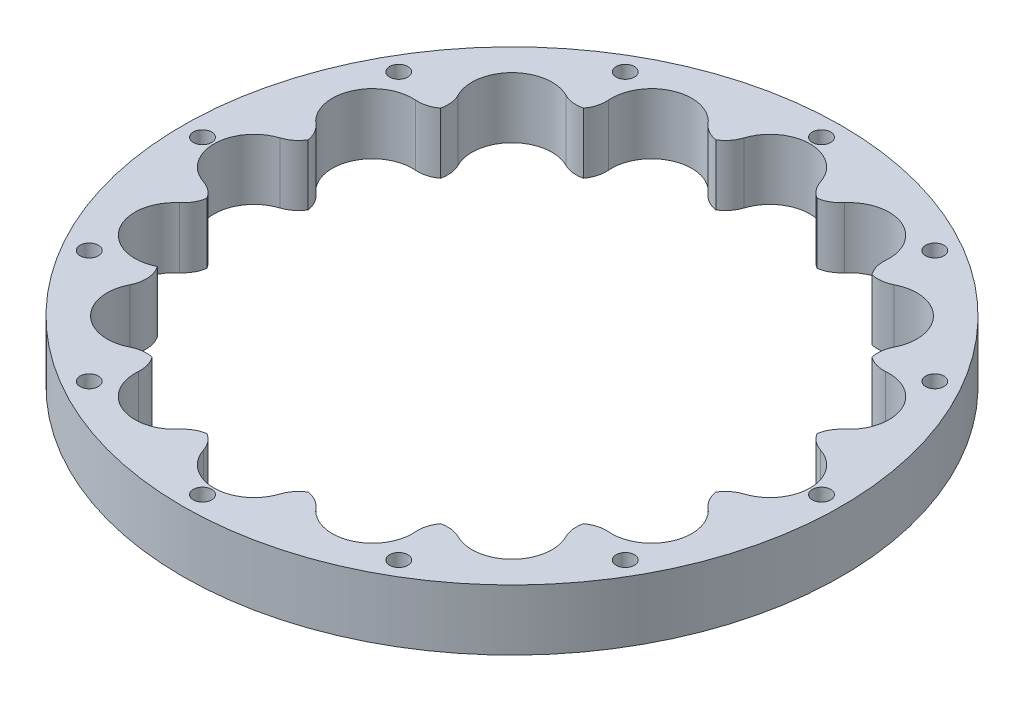
SolidWorks part; units mm, degrees
ref_plane "Front Plane" through (0, 0, 0) normal (0, 0, 1) x (1, 0, 0)
ref_plane "Top Plane" through (0, 0, 0) normal (0, 1, 0) x (1, 0, 0)
ref_plane "Right Plane" through (0, 0, 0) normal (1, 0, 0) x (0, 0, -1)
sketch "Sketch1" plane through (0, 0, 0) normal (0, 1, 0) x (1, 0, 0)
  circle A0 centre (0, 0) radius 45
  circle A1 centre (0, 45) radius 7
  circle A2 centre (17.2208, 41.5746) radius 7
  circle A3 centre (31.8198, 31.8198) radius 7
  circle A4 centre (41.5746, 17.2208) radius 7
  circle A5 centre (45, 0) radius 7
  circle A6 centre (41.5746, -17.2208) radius 7
  circle A7 centre (31.8198, -31.8198) radius 7
  circle A8 centre (17.2208, -41.5746) radius 7
  circle A9 centre (0, -45) radius 7
  circle A10 centre (-17.2208, -41.5746) radius 7
  circle A11 centre (-31.8198, -31.8198) radius 7
  circle A12 centre (0, 0) radius 57.5
  circle A13 centre (0, 0) radius 54 construction
  circle A14 centre (0, 54) radius 1.6
  circle A15 centre (27, 46.7654) radius 1.6
  circle A16 centre (46.7654, 27) radius 1.6
  circle A17 centre (54, 0) radius 1.6
  circle A18 centre (46.7654, -27) radius 1.6
  circle A19 centre (27, -46.7654) radius 1.6
  circle A20 centre (0, -54) radius 1.6
  circle A21 centre (-27, -46.7654) radius 1.6
  circle A22 centre (-46.7654, -27) radius 1.6
  circle A23 centre (-54, 0) radius 1.6
  circle A24 centre (-46.7654, 27) radius 1.6
  circle A25 centre (-27, 46.7654) radius 1.6
  circle A26 centre (-41.5746, -17.2208) radius 7
  circle A27 centre (-45, 0) radius 7
  circle A28 centre (-41.5746, 17.2208) radius 7
  circle A29 centre (-31.8198, 31.8198) radius 7
  circle A30 centre (-17.2208, 41.5746) radius 7
  point P27 (0, 0)
  point P54 (0, 0)
  dimension "D1" = 90
  dimension "D2" = 14
  dimension "D4" = 115
  dimension "D5" = 108
  dimension "D6" = 3.2
  dimension "D3" = 16
  dimension "D7" = 12
extrude "Boss-Extrude1" add sketch "Sketch1" along normal blind 10.6 contours A12 A25 A24 A23 A22 A21 A20 A19 A18 A17 A16 A15 A14 A11 A0 A1 A2 A3 A4 A5 A6 A7 A8 A9 A10 region at (-55.8737, 0, 0)
fillet "Fillet1" radius 5 31 edges at (38.4009, 5.3, -23.46) (36.3696, 5.3, -26.5001) (44.4556, 5.3, -6.9788) (43.7422, 5.3, -10.5648) (44.4556, 5.3, 6.9788) (43.7422, 5.3, 10.5648) (38.4009, 5.3, 23.46) (36.3696, 5.3, 26.5001) (26.5001, 5.3, 36.3696) (23.46, 5.3, 38.4009) (6.9788, 5.3, 44.4556) (10.5648, 5.3, 43.7422) (-6.9788, 5.3, 44.4556) (-10.5648, 5.3, 43.7422) (-23.46, 5.3, 38.4009) (-26.5001, 5.3, 36.3696) (26.5001, 5.3, -36.3696) (23.46, 5.3, -38.4009) (10.5648, 5.3, -43.7422) (6.9788, 5.3, -44.4556) (-6.9788, 5.3, -44.4556) (-36.3696, 5.3, 26.5001) (-10.5648, 5.3, -43.7422) (-23.46, 5.3, -38.4009) (-26.5001, 5.3, -36.3696) (-36.3696, 5.3, -26.5001) (-38.4009, 5.3, -23.46) (-43.7422, 5.3, -10.5648) (-44.4556, 5.3, -6.9788) (-44.4556, 5.3, 6.9788) (-43.7422, 5.3, 10.5648)
